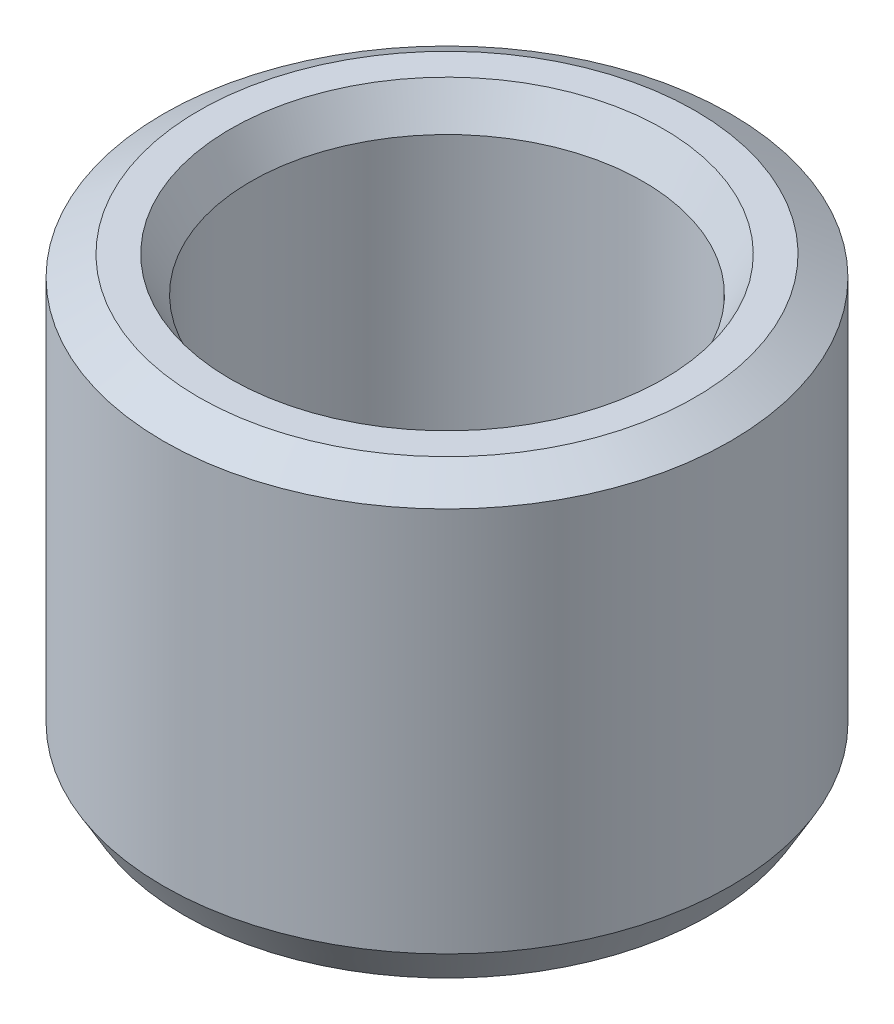
SolidWorks part; units mm, degrees
ref_plane "Front Plane" through (0, 0, 0) normal (0, 0, 1) x (1, 0, 0)
ref_plane "Top Plane" through (0, 0, 0) normal (0, 1, 0) x (1, 0, 0)
ref_plane "Right Plane" through (0, 0, 0) normal (1, 0, 0) x (0, 0, -1)
sketch "Sketch1" plane through (0, 0, 0) normal (0, 1, 0) x (1, 0, 0)
  circle A0 centre (0, 0) radius 50
  dimension "SLEEVE_OD" = 100
extrude "Boss-Extrude1" add sketch "Sketch1" along normal blind 77.7686
sketch "Sketch2" plane through (0, 0, 0) normal (0, 1, 0) x (1, 0, 0)
  circle A0 centre (0, 0) radius 34.6019
  dimension "BORE_D" = 69.2039
extrude "Cut-Extrude1" cut sketch "Sketch2" along normal through all
chamfer "Chamfer1" distance 3.5917 angle 60 4 edges at (0, 77.7686, 34.6019) (0, 0, 34.6019) (0, 0, 50) (0, 77.7686, 50) first distance on face at (0, 77.7686, 34.6019) first distance on face at (0, 0, 34.6019) first distance on face at (0, 77.7686, 50)
